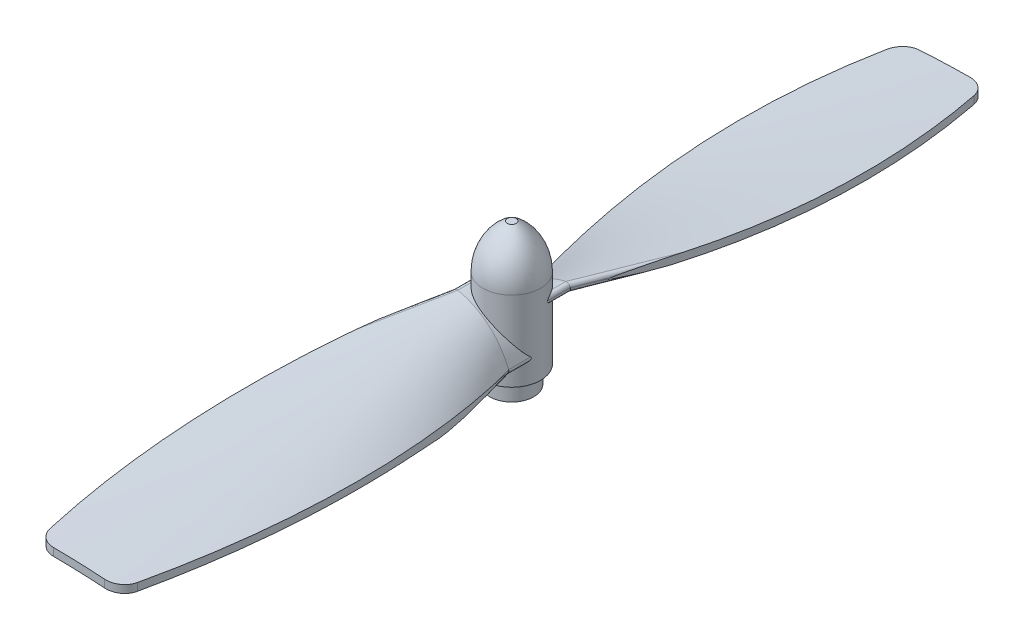
SolidWorks part; units mm, degrees
ref_plane "Front Plane" through (0, 0, 0) normal (0, 0, 1) x (1, 0, 0)
ref_plane "Top Plane" through (0, 0, 0) normal (0, 1, 0) x (1, 0, 0)
ref_plane "Right Plane" through (0, 0, 0) normal (1, 0, 0) x (0, 0, -1)
sketch "Sketch5" plane through (0, 0, 0) normal (0, 0, 1) x (1, 0, 0)
  line L0 (0, 8.5598) -> (0, 0) construction
  line L1 (0, 0) -> (-1.9939, 0)
  line L2 (-1.9939, 0) -> (-1.9939, 5.5191)
  line L3 (-0.3048, 8.5598) -> (0, 8.5598)
  line L4 (0, 8.5598) -> (0, 0)
  arc A0 (-1.9939, 5.5191) -> (-0.3048, 8.5598) centre (1.5875, 5.5191) cw
  dimension "D3" = 0.3048
  dimension "D4" = 3.5814
  dimension "D1" = 8.5598
  dimension "D2" = 3.9878
revolve "Revolve2" add sketch "Sketch5" angle 360 about L0
sketch "Sketch6" plane through (0, 0, 0) normal (0, -1, 0) x (1, 0, 0)
  circle A0 centre (0, 0) radius 1.524
  dimension "D1" = 3.048
extrude "Boss-Extrude2" add sketch "Sketch6" along normal blind 1.2192
sketch "Sketch7" plane through (0, -1.2192, 0) normal (0, -1, 0) x (1, 0, 0)
  circle A0 centre (0, 0) radius 0.3937
  dimension "D1" = 0.7874
extrude "Cut-Extrude1" cut sketch "Sketch7" against normal blind 6.858
sketch "Sketch8" plane through (0, 0, 0) normal (0, 0, 1) x (1, 0, 0)
  line L0 (-1.9939, 5.5191) -> (-1.9939, 0) construction
  line L1 (-1.9071, 4.4585) -> (-1.911, 4.4333)
  line L4 (1.7406, 1.3305) -> (1.7164, 1.3228)
  line L5 (-1.9939, 0) -> (1.9939, 0) construction
  line L6 (1.9939, 0) -> (1.9939, 5.5191) construction
  arc A0 (-1.6031, 4.6678) -> (1.9011, 1.6629) centre (-2.6099, -0.052) cw
  arc A1 (-1.7131, 4.1458) -> (1.4021, 1.4746) centre (-2.6099, -0.052) cw
  arc A2 (-1.949, 4.1894) -> (1.4811, 1.248) centre (-2.6099, -0.052) cw construction
  arc A3 (-1.7131, 4.1458) -> (-1.911, 4.4333) centre (-1.66, 4.3942) cw
  arc A4 (-1.8669, 4.7164) -> (1.9894, 1.4096) centre (-2.6099, -0.052) cw construction
  arc A5 (-1.9071, 4.4585) -> (-1.6031, 4.6678) centre (-1.6561, 4.4194) cw
  arc A6 (1.7164, 1.3228) -> (1.4021, 1.4746) centre (1.6395, 1.5649) cw
  arc A7 (1.7406, 1.3305) -> (1.9011, 1.6629) centre (1.6637, 1.5726) ccw
  point P19 (-1.8669, 4.7164)
  dimension "D1" = 1.5649
  dimension "D5" = 4.826
  dimension "D7" = 0.254
  dimension "D2" = 0.127
  dimension "D3" = 4.3599
  dimension "D4" = 0.0762
  dimension "D6" = 0.5334
ref_plane "Plane1" through (0, 0, 2.1209) normal (0, 0, 1) x (1, 0, 0)
sketch "Sketch9" plane through (0, 0, 2.1209) normal (0, 0, 1) x (1, 0, 0)
  line L2 (-1.9071, 4.4585) -> (-1.911, 4.4333)
  line L3 (1.7164, 1.3228) -> (1.7406, 1.3305)
  line L4 (-1.9071, 4.4585) -> (-1.911, 4.4333)
  line L5 (1.7164, 1.3228) -> (1.7406, 1.3305)
  arc A6 (-1.911, 4.4333) -> (-1.7131, 4.1458) centre (-1.66, 4.3942) ccw
  arc A7 (1.4021, 1.4746) -> (-1.7131, 4.1458) centre (-2.6099, -0.052) ccw
  arc A8 (1.4021, 1.4746) -> (1.7164, 1.3228) centre (1.6395, 1.5649) ccw
  arc A9 (1.7406, 1.3305) -> (1.9011, 1.6629) centre (1.6637, 1.5726) ccw
  arc A10 (1.9011, 1.6629) -> (-1.6031, 4.6678) centre (-2.6099, -0.052) ccw
  arc A11 (-1.6031, 4.6678) -> (-1.9071, 4.4585) centre (-1.6561, 4.4194) ccw
  arc A12 (-1.911, 4.4333) -> (-1.7131, 4.1458) centre (-1.66, 4.3942) ccw
  arc A13 (1.4021, 1.4746) -> (-1.7131, 4.1458) centre (-2.6099, -0.052) ccw
  arc A14 (1.4021, 1.4746) -> (1.7164, 1.3228) centre (1.6395, 1.5649) ccw
  arc A15 (1.7406, 1.3305) -> (1.9011, 1.6629) centre (1.6637, 1.5726) ccw
  arc A16 (1.9011, 1.6629) -> (-1.6031, 4.6678) centre (-2.6099, -0.052) ccw
  arc A17 (-1.6031, 4.6678) -> (-1.9071, 4.4585) centre (-1.6561, 4.4194) ccw
  dimension "D1" = 0
extrude "Boss-Extrude5" add sketch "Sketch9" against normal up to surface (1.5198 mm away) up to face at (-1.9939, 0, 0)
sketch "Sketch12" plane through (0, 0, 2.1209) normal (0, 0, 1) x (1, 0, 0)
  line L2 (-1.9071, 4.4585) -> (-1.911, 4.4333)
  line L3 (1.7164, 1.3228) -> (1.7406, 1.3305)
  line L4 (-1.9071, 4.4585) -> (-1.911, 4.4333)
  line L5 (1.7164, 1.3228) -> (1.7406, 1.3305)
  arc A6 (-1.6031, 4.6678) -> (-1.9071, 4.4585) centre (-1.6561, 4.4194) ccw
  arc A7 (-1.911, 4.4333) -> (-1.7131, 4.1458) centre (-1.66, 4.3942) ccw
  arc A8 (1.4021, 1.4746) -> (-1.7131, 4.1458) centre (-2.6099, -0.052) ccw
  arc A9 (1.4021, 1.4746) -> (1.7164, 1.3228) centre (1.6395, 1.5649) ccw
  arc A10 (1.7406, 1.3305) -> (1.9011, 1.6629) centre (1.6637, 1.5726) ccw
  arc A11 (1.9011, 1.6629) -> (-1.6031, 4.6678) centre (-2.6099, -0.052) ccw
  arc A12 (-1.6031, 4.6678) -> (-1.9071, 4.4585) centre (-1.6561, 4.4194) ccw
  arc A13 (-1.911, 4.4333) -> (-1.7131, 4.1458) centre (-1.66, 4.3942) ccw
  arc A14 (1.4021, 1.4746) -> (-1.7131, 4.1458) centre (-2.6099, -0.052) ccw
  arc A15 (1.4021, 1.4746) -> (1.7164, 1.3228) centre (1.6395, 1.5649) ccw
  arc A16 (1.7406, 1.3305) -> (1.9011, 1.6629) centre (1.6637, 1.5726) ccw
  arc A17 (1.9011, 1.6629) -> (-1.6031, 4.6678) centre (-2.6099, -0.052) ccw
  dimension "D1" = 0
ref_plane "Plane2" through (0, 0, 29.9339) normal (0, 0, 1) x (1, 0, 0)
sketch "Sketch10" plane through (0, 0, 29.9339) normal (0, 0, 1) x (1, 0, 0)
  line L0 (-9.902, 2.2621) -> (-9.8971, 2.2371)
  line L1 (9.9179, 1.5331) -> (9.9112, 1.5086)
  line L2 (-1.9939, 0) -> (1.9939, 0) construction
  arc A0 (-9.6867, 2.5627) -> (9.7253, 1.8487) centre (-2.0506, -54.0749) cw
  arc A1 (-9.6139, 2.0343) -> (9.6139, 1.3271) centre (-2.0506, -54.0749) cw
  arc A2 (10.0852, 1.7717) -> (44.8222, -21.3784) centre (-2.0506, -54.0749) cw construction
  arc A3 (9.7253, 1.8487) -> (9.9179, 1.5331) centre (9.673, 1.6002) cw
  arc A4 (9.972, 1.2505) -> (44.3847, -21.6835) centre (-2.0506, -54.0749) cw construction
  arc A5 (9.6139, 1.3271) -> (9.9112, 1.5086) centre (9.6662, 1.5757) ccw
  arc A6 (-9.6139, 2.0343) -> (-9.8971, 2.2371) centre (-9.6478, 2.286) cw
  arc A7 (-9.902, 2.2621) -> (-9.6867, 2.5627) centre (-9.6527, 2.311) cw
  dimension "D1" = 0.5334
  dimension "D3" = 0.0254
  dimension "D2" = 0.254
  dimension "D8" = 57.15
  dimension "D9" = 56.6166
  dimension "D12" = 57.15
  dimension "D4" = 1.6002
  dimension "D5" = 7.62
  dimension "D6" = 7.62
  dimension "D7" = 2.286
  dimension "D10" = 19.412
  dimension "D11" = 2.0343
loft "Loft8" add profiles "Sketch12", "Sketch10"
sketch "Sketch16" plane through (0, 0, 0) normal (0, 1, 0) x (1, 0, 0)
  line L0 (-9.6139, -29.9339) -> (9.6139, -29.9339) construction
  line L1 (0, -29.9339) -> (0, 0) construction
  line L2 (-3.9751, -17.6395) -> (3.9751, -17.6395) construction
  line L3 (-2.794, -29.9339) -> (2.794, -29.9339)
  line L4 (-1.913, -2.1225) -> (-8.4919, 0)
  line L5 (-8.4919, 0) -> (0, 7.6754)
  line L6 (0, 7.6754) -> (8.2412, 0)
  line L7 (8.2412, 0) -> (1.913, -2.1225)
  line L8 (1.913, -2.1225) -> (1.8566, -2.1929)
  arc A0 (-1.913, -2.1225) -> (-2.794, -29.9339) centre (52.7047, -17.7724) ccw
  arc A1 (1.913, -2.1225) -> (2.794, -29.9339) centre (-52.7047, -17.7724) cw
  spline S7 degree 3 poles (-1.913, -2.1225) (-2.1875, -3.0807) (-2.6307, -4.6275) (-3.2325, -6.7273) (-3.7136, -8.4055) (-4.1081, -9.7814) (-4.4301, -10.9042) (-4.6817, -11.7819) (-4.9379, -12.6744) (-5.1341, -13.3615) (-5.2783, -13.8602) (-5.3693, -14.1684) (-5.4313, -14.3822) (-5.4635, -14.493) knots 0 0 0 0 0.232381 0.37512 0.509246 0.639395 0.708811 0.781576 0.852266 0.925268 0.948253 0.973171 1 1 1 1 construction
  point P8 (0, -17.6395)
  point P9 (0, -29.9339)
  dimension "D1" = 5.588
  dimension "D2" = 7.9502
extrude "Cut-Extrude4" cut sketch "Sketch16" along normal blind 6.858 flip side to cut contours A1 L7 L6 L5 L4 A0 L3 region at (-0.025, 0, 11.0061)
fillet "Fillet3" radius 1.27 2 edges
ref_plane "Plane4" through (0, 0, -2.1336) normal (0, 0, 1) x (1, 0, 0)
sketch "Sketch17" plane through (0, 0, -2.1336) normal (0, 0, 1) x (1, 0, 0)
  line L0 (1.9108, 4.4585) -> (1.9147, 4.4333)
  line L2 (-1.7127, 1.3228) -> (-1.737, 1.3305)
  arc A0 (-1.8975, 1.6629) -> (1.6068, 4.6678) centre (2.6136, -0.052) cw
  arc A1 (-1.3984, 1.4746) -> (1.7168, 4.1458) centre (2.6136, -0.052) cw
  arc A2 (-2.1829, 0.4807) -> (2.2084, 4.7569) centre (2.6136, -0.052) cw construction
  arc A3 (-1.8975, 1.6629) -> (-1.737, 1.3305) centre (-1.66, 1.5726) ccw
  arc A4 (-1.6528, 0.4218) -> (2.2531, 4.2254) centre (2.6136, -0.052) cw construction
  arc A5 (-1.3984, 1.4746) -> (-1.7127, 1.3228) centre (-1.6358, 1.5649) cw
  arc A6 (1.7168, 4.1458) -> (1.9147, 4.4333) centre (1.6637, 4.3942) ccw
  arc A7 (1.6068, 4.6678) -> (1.9108, 4.4585) centre (1.6598, 4.4194) cw
  arc A8 (1.9011, 1.6629) -> (-1.6031, 4.6678) centre (-2.6099, -0.052) ccw construction
  dimension "D1" = 0.5334
  dimension "D2" = 0.254
extrude "Boss-Extrude6" add sketch "Sketch17" along normal up to surface (0.953 mm away) up to face at (-0.0709, 3.1243, 1.0945)
sketch "Sketch19" plane through (0, 0, -2.1336) normal (0, 0, -1) x (-1, 0, 0)
  line L2 (-1.9108, 4.4585) -> (-1.9147, 4.4333)
  line L3 (1.7127, 1.3228) -> (1.737, 1.3305)
  line L4 (-1.9108, 4.4585) -> (-1.9147, 4.4333)
  line L5 (1.7127, 1.3228) -> (1.737, 1.3305)
  arc A6 (1.737, 1.3305) -> (1.8975, 1.6629) centre (1.66, 1.5726) ccw
  arc A7 (1.8975, 1.6629) -> (-1.6068, 4.6678) centre (-2.6136, -0.052) ccw
  arc A8 (-1.6068, 4.6678) -> (-1.9108, 4.4585) centre (-1.6598, 4.4194) ccw
  arc A9 (-1.9147, 4.4333) -> (-1.7168, 4.1458) centre (-1.6637, 4.3942) ccw
  arc A10 (1.3984, 1.4746) -> (-1.7168, 4.1458) centre (-2.6136, -0.052) ccw
  arc A11 (1.3984, 1.4746) -> (1.7127, 1.3228) centre (1.6358, 1.5649) ccw
  arc A12 (1.737, 1.3305) -> (1.8975, 1.6629) centre (1.66, 1.5726) ccw
  arc A13 (1.8975, 1.6629) -> (-1.6068, 4.6678) centre (-2.6136, -0.052) ccw
  arc A14 (-1.6068, 4.6678) -> (-1.9108, 4.4585) centre (-1.6598, 4.4194) ccw
  arc A15 (-1.9147, 4.4333) -> (-1.7168, 4.1458) centre (-1.6637, 4.3942) ccw
  arc A16 (1.3984, 1.4746) -> (-1.7168, 4.1458) centre (-2.6136, -0.052) ccw
  arc A17 (1.3984, 1.4746) -> (1.7127, 1.3228) centre (1.6358, 1.5649) ccw
  dimension "D1" = 0
ref_plane "Plane5" through (0, 0, -29.9466) normal (0, 0, 1) x (1, 0, 0)
sketch "Sketch18" plane through (0, 0, -29.9466) normal (0, 0, 1) x (1, 0, 0)
  line L0 (9.9181, 2.2443) -> (9.9113, 2.2196)
  line L1 (-9.902, 1.5516) -> (-9.8971, 1.5267)
  arc A0 (9.7069, 2.5627) -> (-9.7051, 1.8491) centre (2.0697, -54.0747) ccw
  arc A1 (9.6323, 2.0345) -> (-9.5955, 1.3271) centre (2.0697, -54.0747) ccw
  arc A2 (5.3284, 2.9823) -> (-13.4456, 0.9289) centre (2.0697, -54.0747) ccw construction
  arc A3 (-9.7051, 1.8491) -> (-9.902, 1.5516) centre (-9.6527, 1.6006) ccw
  arc A4 (5.298, 2.4498) -> (-13.3008, 0.4155) centre (2.0697, -54.0747) ccw construction
  arc A5 (-9.5955, 1.3271) -> (-9.8971, 1.5267) centre (-9.6478, 1.5757) cw
  arc A6 (9.6323, 2.0345) -> (9.9113, 2.2196) centre (9.6662, 2.2862) ccw
  arc A7 (9.7069, 2.5627) -> (9.9181, 2.2443) centre (9.673, 2.311) cw
  arc A8 (9.7253, 1.8487) -> (-9.6867, 2.5627) centre (-2.0506, -54.0749) ccw construction
  dimension "D1" = 0.5334
  dimension "D2" = 0.254
loft "Loft9" add profiles "Sketch19", "Sketch18"
sketch "Sketch23" plane through (0, 0, 0) normal (0, 1, 0) x (1, 0, 0)
  line L0 (9.7069, 29.9466) -> (-9.7051, 29.9466) construction
  line L1 (0.0009, 29.9466) -> (0, 0) construction
  line L2 (-2.7931, 29.9466) -> (2.7949, 29.9466)
  line L3 (-2.794, -29.9339) -> (2.794, -29.9339) construction
  line L4 (-1.8975, 2.1336) -> (-15.4919, 1.5757)
  line L5 (-15.4919, 1.5757) -> (-29.847, 37.9053)
  line L6 (-29.847, 37.9053) -> (30.7227, 36.1333)
  line L7 (30.7227, 36.1333) -> (1.9177, 2.1346)
  arc A0 (-1.8975, 2.1336) -> (-2.7931, 29.9466) centre (48.3151, 17.6714) cw
  arc A1 (2.7949, 29.9466) -> (1.9177, 2.1346) centre (-48.3053, 17.6385) cw
  spline S14 degree 3 poles (-9.9054, 29.9466) (-9.5868, 28.8537) (-9.0982, 27.178) (-8.4414, 24.919) (-8.0184, 23.4617) (-7.6807, 22.2958) (-7.4335, 21.4415) (-7.2018, 20.64) (-6.9856, 19.8912) (-6.7696, 19.1425) (-6.4547, 18.0496) (-6.0478, 16.6354) (-5.4438, 14.5318) (-4.8443, 12.4381) (-4.2687, 10.4229) (-3.8913, 9.0996) (-3.575, 7.9886) (-3.2947, 7.0033) (-2.9394, 5.7533) (-2.4795, 4.1326) (-2.1211, 2.8675) (-1.914, 2.1362) knots 0 0 0 0 0.118031 0.18097 0.243899 0.275359 0.306817 0.336103 0.361863 0.387615 0.416896 0.479784 0.540179 0.643802 0.705577 0.757467 0.786468 0.825335 0.863678 0.9212 1 1 1 1 construction
  point P8 (0.0009, 29.9466)
extrude "Cut-Extrude6" cut sketch "Sketch23" along normal blind 6.858
fillet "Fillet7" radius 1.27 2 edges
equation "\"D5@Sketch10\"=\"D6@Sketch10\""
